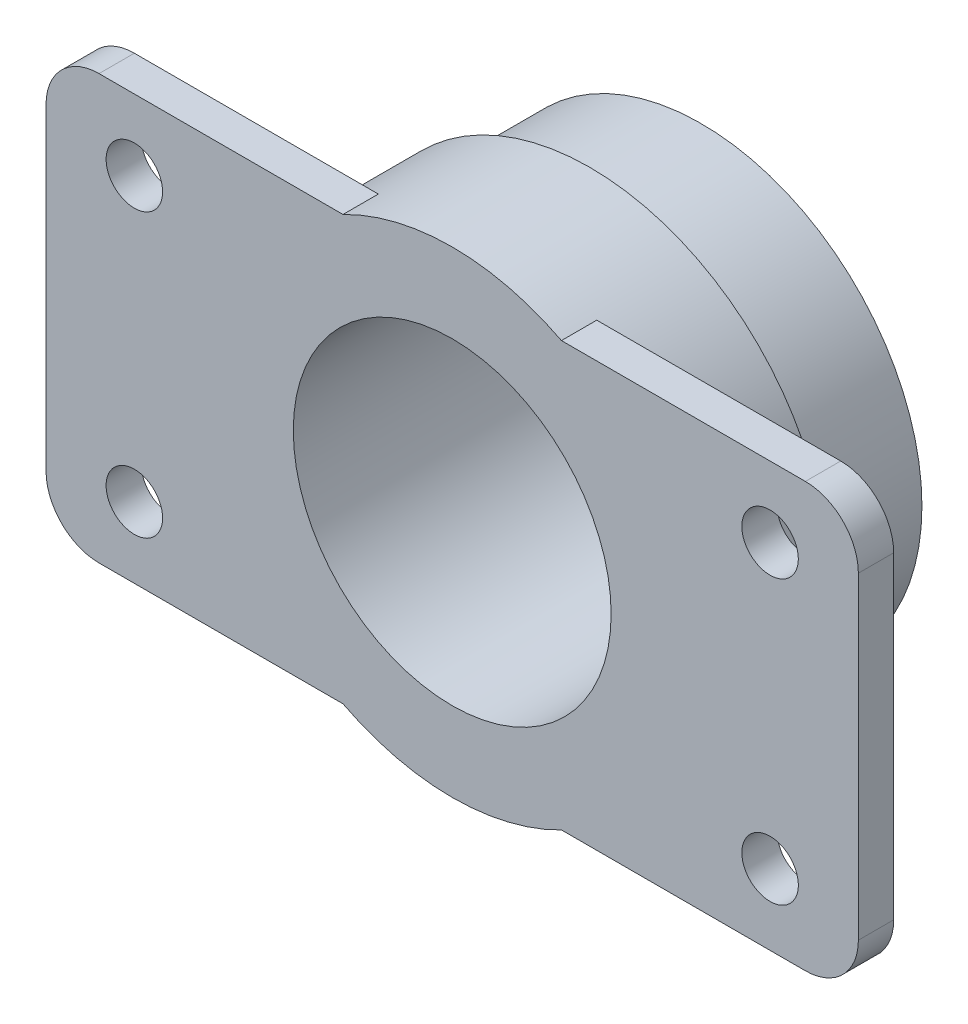
SolidWorks part; units mm, degrees
material "6061 合金"
ref_plane "前视基准面" through (0, 0, 0) normal (0, 0, 1) x (1, 0, 0)
ref_plane "上视基准面" through (0, 0, 0) normal (0, 1, 0) x (1, 0, 0)
ref_plane "右视基准面" through (0, 0, 0) normal (1, 0, 0) x (0, 0, -1)
sketch "草图1" plane through (0, 0, 0) normal (0, 0, 1) x (1, 0, 0)
  circle A0 centre (0, 0) radius 9
  circle A1 centre (0, 0) radius 12.5
  dimension "D1" = 18
  dimension "D2" = 25
extrude "凸台-拉伸1" add sketch "草图1" along normal blind 6.3
sketch "草图2" plane through (0, 0, 6.3) normal (0, 0, 1) x (1, 0, 0)
  circle A0 centre (0, 0) radius 9 construction
  circle A1 centre (0, 0) radius 9
  circle A2 centre (0, 0) radius 13.5
  dimension "D1" = 27
extrude "凸台-拉伸2" add sketch "草图2" along normal blind 5.8
sketch "草图3" plane through (0, 0, 12.1) normal (0, 0, 1) x (1, 0, 0)
  line L0 (-23, 12) -> (-23, -12)
  line L1 (-23, -12) -> (23, -12)
  line L2 (23, -12) -> (23, 12)
  line L3 (23, 12) -> (-23, 12)
  line L4 (0, 0) -> (-9, 0) construction
  line L5 (0, 0) -> (0, -12) construction
  circle A0 centre (0, 0) radius 9 construction
  circle A1 centre (0, 0) radius 9
  circle A2 centre (18, 8) radius 1.6
  circle A3 centre (18, -8) radius 1.6
  circle A4 centre (-18, -8) radius 1.6
  circle A5 centre (-18, 8) radius 1.6
  dimension "D5" = 3.2
  dimension "D4" = 16
  dimension "D1" = 46
  dimension "D2" = 36
  dimension "D3" = 24
extrude "凸台-拉伸3" add sketch "草图3" along normal blind 2
fillet "圆角1" radius 3 4 edges at (23, -12, 13.1) (-23, -12, 13.1) (-23, 12, 13.1) (23, 12, 13.1)
sketch "草图4" plane through (0, 0, 12.1) normal (0, 0, 1) x (1, 0, 0)
  line L0 (-20, -12) -> (20, -12) construction
  line L1 (20, 12) -> (-20, 12) construction
  line L2 (-20, -12) -> (20, -12)
  line L3 (20, 12) -> (-20, 12)
  arc A0 (-6.1847, -12) -> (6.1847, -12) centre (0, 0) ccw construction
  arc A1 (6.1847, 12) -> (-6.1847, 12) centre (0, 0) ccw construction
  arc A2 (-6.1847, -12) -> (6.1847, -12) centre (0, 0) ccw
  arc A3 (6.1847, 12) -> (-6.1847, 12) centre (0, 0) ccw
  line M1 (-6.1847, 12) -> (6.1847, 12)
  arc M2 (6.1847, 12) -> (-6.1847, 12) centre (0, 0) ccw
extrude "凸台-拉伸4" add sketch "草图4" along normal up to surface (2 mm away) contours M2 M1 | L2 A2 region at (0, -12.603, 12.1) region at (0, 12.603, 12.1) up to face at (-16.4, -8, 14.1)
